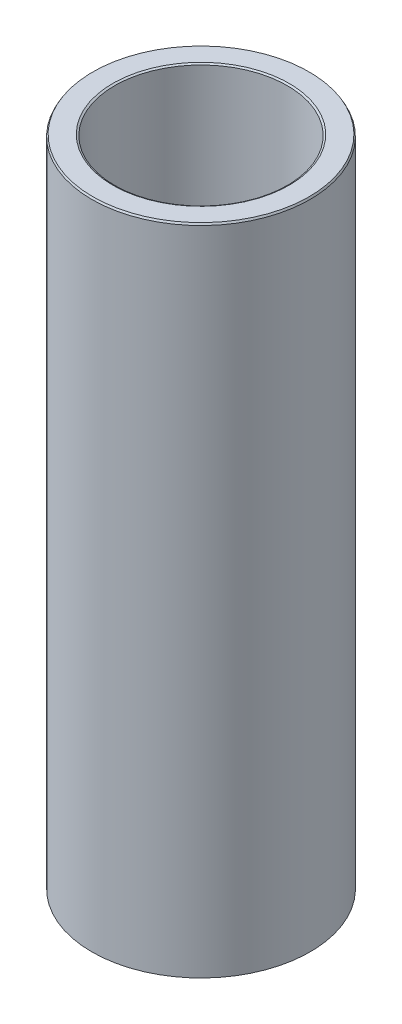
SolidWorks part; units mm, degrees
ref_plane "Front Plane" through (0, 0, 0) normal (0, 0, 1) x (1, 0, 0)
ref_plane "Top Plane" through (0, 0, 0) normal (0, 1, 0) x (1, 0, 0)
ref_plane "Right Plane" through (0, 0, 0) normal (1, 0, 0) x (0, 0, -1)
sketch "Sketch1" plane through (0, 0, 0) normal (0, 1, 0) x (1, 0, 0)
  circle A0 centre (0, 0) radius 37.5
  dimension "SLEEVE_OD" = 75
extrude "Boss-Extrude1" add sketch "Sketch1" along normal blind 224.7557
sketch "Sketch2" plane through (0, 0, 0) normal (0, 1, 0) x (1, 0, 0)
  circle A0 centre (0, 0) radius 29.6706
  dimension "BORE_D" = 59.3412
extrude "Cut-Extrude1" cut sketch "Sketch2" along normal through all
chamfer "Chamfer1" distance 0.6216 angle 30 4 edges at (0, 224.7557, 29.6706) (0, 0, 29.6706) (0, 0, 37.5) (0, 224.7557, 37.5) first distance on face at (0, 224.7557, 29.6706) first distance on face at (0, 0, 29.6706) first distance on face at (0, 224.7557, 37.5)
